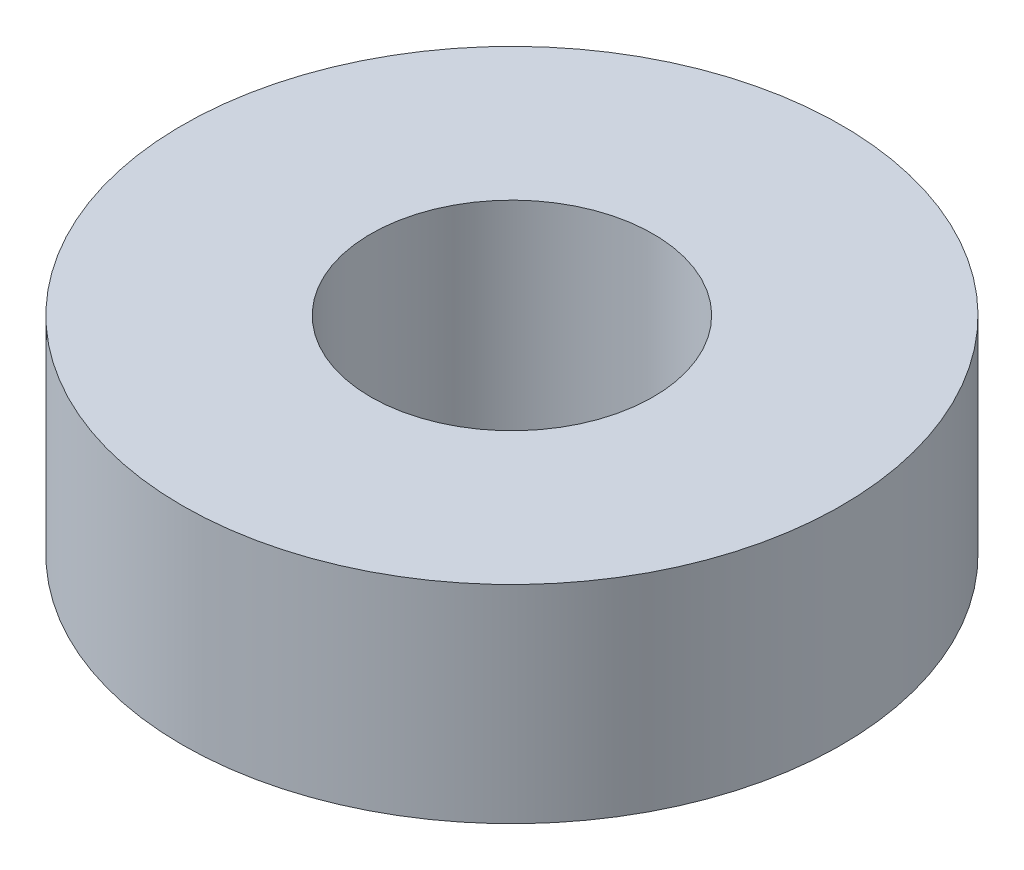
SolidWorks part; units mm, degrees
ref_plane "Front Plane" through (0, 0, 0) normal (0, 0, 1) x (1, 0, 0)
ref_plane "Top Plane" through (0, 0, 0) normal (0, 1, 0) x (1, 0, 0)
ref_plane "Right Plane" through (0, 0, 0) normal (1, 0, 0) x (0, 0, -1)
sketch "Sketch3" plane through (0, 0, 0) normal (0, 1, 0) x (1, 0, 0)
  circle A0 centre (0, 0) radius 7.5
  circle A1 centre (0, 0) radius 17.5
  dimension "D1" = 15
  dimension "D2" = 35
extrude "Boss-Extrude1" add sketch "Sketch3" along normal blind 11
ref_axis "Axis1" through (0, 11, 0) along (0, -1, 0)
